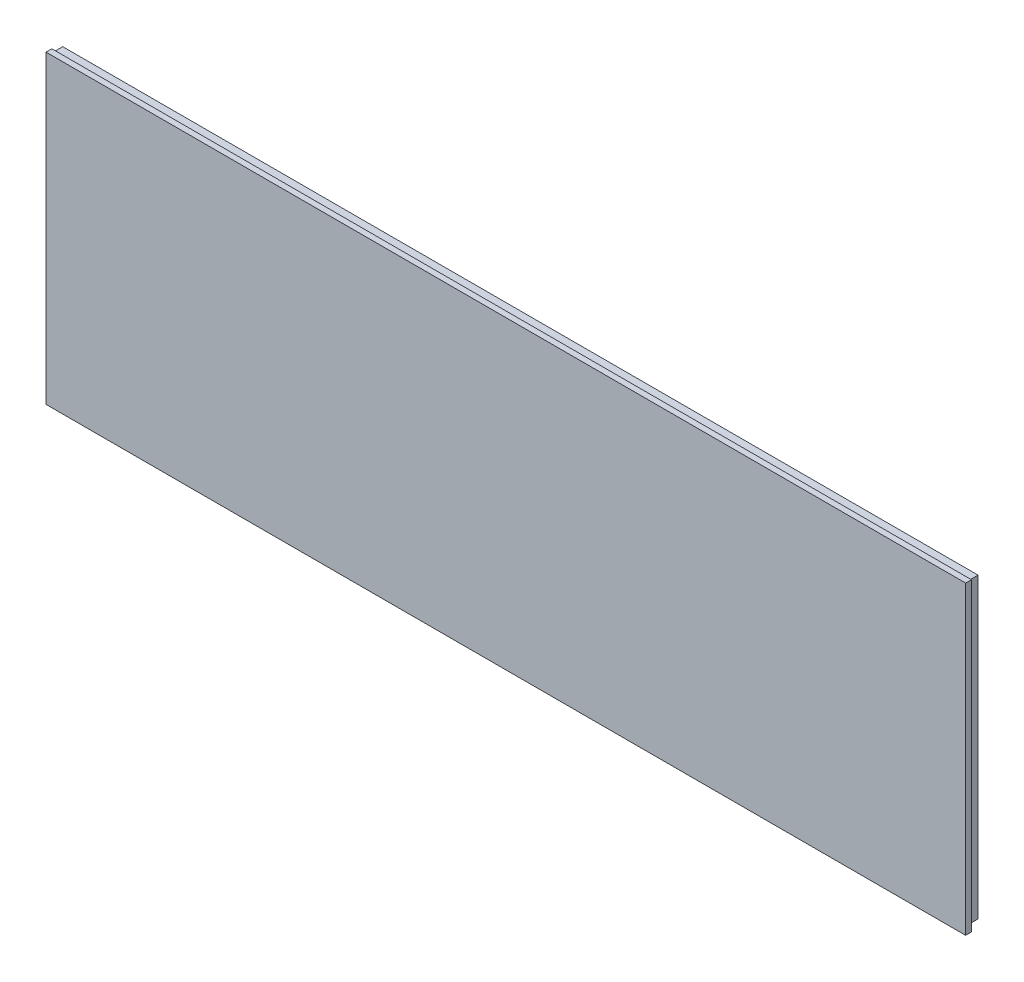
SolidWorks part; units mm, degrees
ref_plane "Front Plane" through (0, 0, 0) normal (0, 0, 1) x (1, 0, 0)
ref_plane "Top Plane" through (0, 0, 0) normal (0, 1, 0) x (1, 0, 0)
ref_plane "Right Plane" through (0, 0, 0) normal (1, 0, 0) x (0, 0, -1)
sketch "Sketch1" plane through (0, 0, 0) normal (0, 0, 1) x (1, 0, 0)
  line L5 (-158.25, 52.5) -> (158.25, 52.5)
  line L6 (-158.25, 52.5) -> (-158.25, -52.5)
  line L7 (-158.25, -52.5) -> (158.25, -52.5)
  line L8 (158.25, 52.5) -> (158.25, -52.5)
  line L9 (-158.25, 52.5) -> (158.25, -52.5) construction
  line L10 (-158.25, -52.5) -> (158.25, 52.5) construction
  point P0 (0, 0)
  dimension "D1" = 105
  dimension "D2" = 316.5
extrude "DIGITIZER" add sketch "Sketch1" along normal blind 2
sketch "Sketch2" plane through (0, 0, 0) normal (0, 0, -1) x (-1, 0, 0)
  line L0 (158.25, -52.5) -> (-158.25, -52.5) construction
  line L5 (-157.5, 52) -> (157.5, 52)
  line L6 (-157.5, 52) -> (-157.5, -50.5)
  line L7 (-157.5, -50.5) -> (157.5, -50.5)
  line L8 (157.5, 52) -> (157.5, -50.5)
  point P4 (0, 52)
  point P6 (-157.5, -49.1893)
  dimension "D1" = 315
  dimension "D2" = 102.5
  dimension "D3" = 2
extrude "DISPLAY INCLUDING ADHESIVE MARGIN OF 1MM" add sketch "Sketch2" along normal blind 3
sketch "Sketch3" plane through (0, 0, 0) normal (0, 0, -1) x (-1, 0, 0)
  line L0 (-157.5, -50.5) -> (157.5, -50.5) construction
  line L1 (-35, -50.5) -> (35, -50.5)
  line L2 (-35, -50.5) -> (-35, -54.5)
  line L3 (-35, -54.5) -> (35, -54.5)
  line L4 (35, -50.5) -> (35, -54.5)
  line L6 (158.25, -52.5) -> (-158.25, -52.5) construction
  point P8 (0, -50.5)
  point P10 (0, 0)
  dimension "D1" = 70
  dimension "D2" = 2
extrude "DIGITIZER CABLE" add sketch "Sketch3" along normal up to surface (3 mm away) up to face at (0, 0.75, -3)
